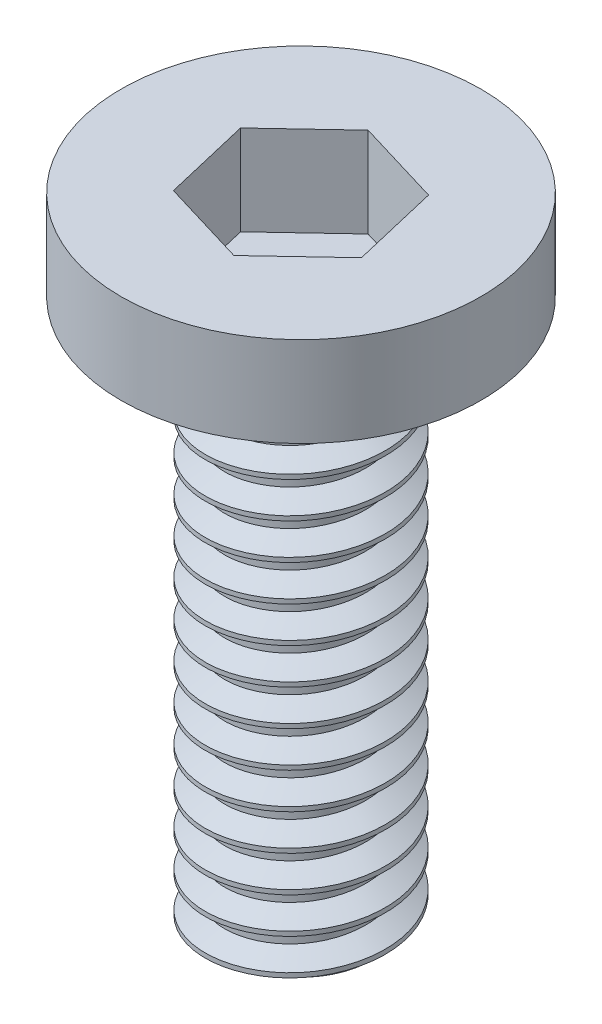
SolidWorks part; units mm, degrees
ref_plane "Ebene vorne" through (0, 0, 0) normal (0, 0, 1) x (1, 0, 0)
ref_plane "Ebene oben" through (0, 0, 0) normal (0, 1, 0) x (1, 0, 0)
ref_plane "Ebene rechts" through (0, 0, 0) normal (1, 0, 0) x (0, 0, -1)
sketch "Skizze1" plane through (0, 0, 0) normal (0, 1, 0) x (1, 0, 0)
  circle A0 centre (0, 0) radius 2
  dimension "D1" = 4
extrude "Aufsatz-Linear austragen1" add sketch "Skizze1" along normal blind 1
sketch "Skizze2" plane through (0, 0, 0) normal (0, -1, 0) x (1, 0, 0)
  circle A0 centre (0, 0) radius 1
  dimension "D1" = 2
extrude "Aufsatz-Linear austragen2" add sketch "Skizze2" along normal blind 6
thread "Gewinde1" pitch 0.4 method cut profile "Gewindeprofil1" start angle 0, offset 0, length 6, pitch 0.4, diameter 2
ref_plane "Ebene1" through (-1, 0, 0) normal (0, 0, 1) x (-1, 0, 0)
sketch "Gewindeprofil1" plane through (-1, 0, 0) normal (0, 0, 1) x (-1, 0, 0)
  line L0 (0, 0) -> (0, 0.4) construction
  line L11 (0, 0) -> (0, 0.35)
  line L12 (0, 0.35) -> (-0.2165, 0.225)
  line L13 (-0.2165, 0.225) -> (-0.2165, 0.125)
  line L15 (-0.2165, 0.125) -> (0, 0)
  line L17 (-0.2165, 0.175) -> (0, 0.175) construction
  point P2 (0, 0)
  dimension "Pitch" = 0.4
  dimension "Profile_Angle" = 60
  dimension "Profile_Land" = 0.1
  dimension "Profile_Height" = 0.2165
sketch "Skizze6" plane through (0, 1, 0) normal (0, 1, 0) x (1, 0, 0)
  line L1 (0.8067, 0.6027) -> (-0.1186, 1)
  line L2 (-0.1186, 1) -> (-0.9253, 0.3973)
  line L3 (-0.9253, 0.3973) -> (-0.8067, -0.6027)
  line L4 (-0.8067, -0.6027) -> (0.1186, -1)
  line L5 (0.1186, -1) -> (0.9253, -0.3973)
  line L6 (0.9253, -0.3973) -> (0.8067, 0.6027)
  circle A0 centre (0, 0) radius 0.8721 construction
  dimension "D1" = 1
extrude "Aufsatz-Linear austragen3" add sketch "Skizze6" against normal blind 1
sketch "Skizze8" plane through (0, 1, 0) normal (0, 1, 0) x (1, 0, 0)
  line L1 (0.7305, 0.6877) -> (-0.2303, 0.9765)
  line L2 (-0.2303, 0.9765) -> (-0.9608, 0.2887)
  line L3 (-0.9608, 0.2887) -> (-0.7305, -0.6877)
  line L4 (-0.7305, -0.6877) -> (0.2303, -0.9765)
  line L5 (0.2303, -0.9765) -> (0.9608, -0.2887)
  line L6 (0.9608, -0.2887) -> (0.7305, 0.6877)
  circle A0 centre (0, 0) radius 0.8689 construction
extrude "Schnitt-Linear austragen1" cut sketch "Skizze8" against normal blind 1
